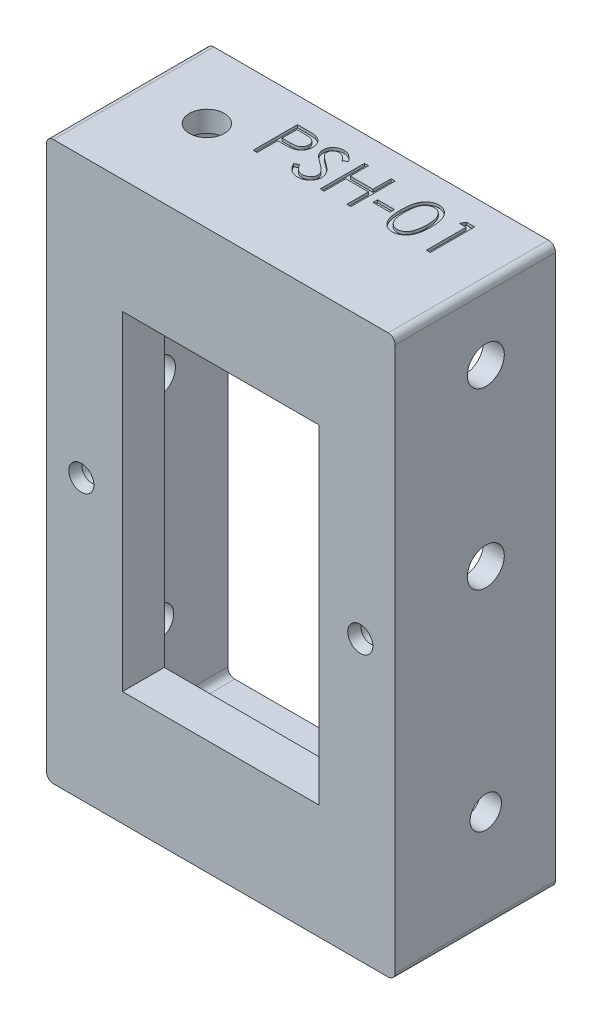
SolidWorks part; units mm, degrees
ref_plane "Front" through (0, 0, 0) normal (0, 0, 1) x (1, 0, 0)
ref_plane "Top" through (0, 0, 0) normal (0, 1, 0) x (1, 0, 0)
ref_plane "Right" through (0, 0, 0) normal (1, 0, 0) x (0, 0, -1)
sketch "Sketch3" plane through (0, 0, 0) normal (0, 0, 1) x (1, 0, 0)
  line L0 (10.9, 16.4) -> (0, 16.4) construction
  line L1 (0, 0) -> (50, 0)
  line L2 (0, 0) -> (0, 80)
  line L3 (0, 80) -> (50, 80)
  line L4 (50, 0) -> (50, 80)
  line L5 (10.9, 16.4) -> (39.1, 16.4)
  line L6 (10.9, 16.4) -> (10.9, 63.6)
  line L7 (10.9, 63.6) -> (39.1, 63.6)
  line L8 (39.1, 16.4) -> (39.1, 63.6)
  line L9 (39.1, 16.4) -> (50, 16.4) construction
  line L10 (10.9, 16.4) -> (10.9, 0) construction
  line L11 (10.9, 63.6) -> (10.9, 80) construction
  line L12 (25, 63.6) -> (25, 40) construction
  line L13 (25, 40) -> (25, 16.4) construction
  line L14 (25, 40) -> (5, 40) construction
  line L15 (25, 40) -> (45, 40) construction
  circle A0 centre (5, 40) radius 1.4
  circle A1 centre (45, 40) radius 1.4
  dimension "D5" = 40
  dimension "D6" = 2.8
  dimension "D1" = 50
  dimension "D2" = 80
  dimension "D3" = 28.2
  dimension "D4" = 47.2
extrude "Boss-Extrude1" add sketch "Sketch3" along normal blind 23
sketch "Sketch4" plane through (0, 0, 0) normal (0, 0, -1) x (-1, 0, 0)
  line L8 (-47, 3) -> (-3, 3)
  line L9 (-3, 3) -> (-3, 77)
  line L10 (-47, 77) -> (-47, 3)
  line L11 (-3, 77) -> (-47, 77)
  line L12 (-47, 3) -> (-3, 3)
  line L13 (-3, 3) -> (-3, 77)
  line L14 (-47, 77) -> (-47, 3)
  line L15 (-3, 77) -> (-47, 77)
  dimension "D1" = 3
extrude "Cut-Extrude1" cut sketch "Sketch4" against normal offset from surface (17 mm away) 6 up to face at (25, 40, 23)
chamfer "Chamfer1" distance 0.4 angle 75 2 edges at (46.4, 40, 23) (6.4, 40, 23) first distance on face at (25, 40, 23)
fillet "Fillet1" radius 1 4 edges at (0, 0, 11.5) (50, 0, 11.5) (50, 80, 11.5) (0, 80, 11.5)
fillet "Fillet2" radius 1 4 edges at (47, 3, 8.5) (3, 3, 8.5) (3, 77, 8.5) (47, 77, 8.5)
sketch "Sketch5" plane through (0, 0, 0) normal (-1, 0, 0) x (0, 0, 1)
  line L0 (0, 79) -> (0, 1) construction
  line L1 (0, 80) -> (23, 80) construction
  line L2 (10, 70) -> (10, 45) construction
  line L3 (10, 45) -> (10, 14.5) construction
  circle A0 centre (10, 70) radius 2.5
  circle A1 centre (10, 45) radius 2.5
  circle A2 centre (10, 14.5) radius 2.25
  dimension "D1" = 10
  dimension "D2" = 5
  dimension "D3" = 10
  dimension "D4" = 25
  dimension "D5" = 14.5
  dimension "D6" = 4.5
extrude "Cut-Extrude2" cut sketch "Sketch5" against normal up to next
hole_wizard "M5 Clearance Hole1" positions "Sketch6" profile "Sketch7" hole size "M5" standard "ANSI Metric" end condition up to next
sketch "Sketch6" plane through (47, 0, 0) normal (-1, 0, 0) x (0, 0, 1)
  point P0 (10, 70)
  point P4 (10, 45)
sketch "Sketch7" plane through (47, 70, 10) normal (0, 1, 0) x (0, 0, 1)
  line L0 (0, 0) -> (0, 3)
  line L1 (0, 3) -> (2.65, 3)
  line L2 (2.65, 3) -> (2.65, 0)
  line L5 (2.65, 0) -> (0, 0)
  line L11 (0, -6.35) -> (0, 107.95) construction
  dimension "Thru Hole Dia." = 5.3
  dimension "Thru Hole Depth" = 3
sketch "Sketch8" plane through (0, 80, 0) normal (0, 1, 0) x (1, 0, 0)
  line L0 (49, 0) -> (1, 0) construction
  line L1 (0, -23) -> (0, 0) construction
  circle A0 centre (10, -10) radius 2.5
  dimension "D1" = 5
  dimension "D3" = 10
  dimension "D2" = 10
extrude "Cut-Extrude3" cut sketch "Sketch8" against normal up to next
hole_wizard "M5 Clearance Hole2" positions "Sketch10" profile "Sketch11" hole size "M5" standard "ANSI Metric" end condition up to next
sketch "Sketch10" plane through (0, 3, 0) normal (0, 1, 0) x (1, 0, 0)
  point P0 (10, -10)
sketch "Sketch11" plane through (10, 3, 10) normal (1, 0, 0) x (0, 0, 1)
  line L0 (0, 0) -> (0, 3)
  line L1 (0, 3) -> (2.65, 3)
  line L2 (2.65, 3) -> (2.65, 0)
  line L5 (2.65, 0) -> (0, 0)
  line L11 (0, -6.35) -> (0, 107.95) construction
  dimension "Thru Hole Dia." = 5.3
  dimension "Thru Hole Depth" = 3
sketch "Sketch12" plane through (47, 0, 0) normal (-1, 0, 0) x (0, 0, 1)
  circle A0 centre (10, 14.5) radius 2.25 construction
  circle A1 centre (10, 14.5) radius 2.25
extrude "Cut-Extrude4" cut sketch "Sketch12" against normal through all
sketch "Sketch13" plane through (0, 80, 0) normal (0, 1, 0) x (1, 0, 0)
  line L0 (10, -10) -> (50, -10) construction
  line L1 (50, 0) -> (50, -23) construction
  text T0 "PSH-01"
extrude "Cut-Extrude5" cut sketch "Sketch13" against normal blind 0.4
sketch "Sketch14" plane through (0, 0, 23) normal (0, 0, 1) x (1, 0, 0)
  line L1 (10.25, 68.5) -> (39.75, 68.5)
  line L2 (10.25, 68.5) -> (10.25, 11.5)
  line L3 (10.25, 11.5) -> (39.75, 11.5)
  line L4 (39.75, 68.5) -> (39.75, 11.5)
  line L6 (25, 68.5) -> (25, 63.6) construction
  line L7 (39.1, 63.6) -> (10.9, 63.6) construction
  line L8 (25, 11.5) -> (25, 16.4) construction
  line L9 (10.9, 16.4) -> (39.1, 16.4) construction
  dimension "D1" = 57
  dimension "D2" = 29.5
extrude "Cut-Extrude6" [suppressed] cut sketch "Sketch14" against normal through all
